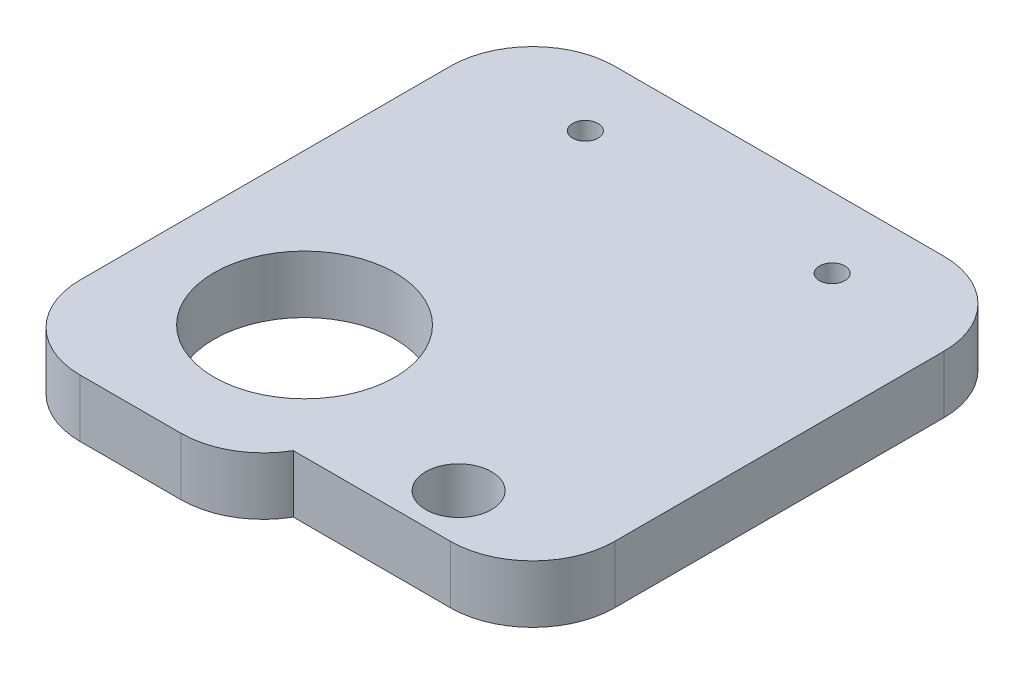
SolidWorks part; units mm, degrees
ref_plane "前视基准面" through (0, 0, 0) normal (0, 0, 1) x (1, 0, 0)
ref_plane "上视基准面" through (0, 0, 0) normal (0, 1, 0) x (1, 0, 0)
ref_plane "右视基准面" through (0, 0, 0) normal (1, 0, 0) x (0, 0, -1)
sketch "草图1" plane through (0, 0, 0) normal (0, 1, 0) x (1, 0, 0)
  line L1 (-25.5, 6.5625) -> (34.5, 6.5625)
  line L2 (-25.5, 6.5625) -> (-25.5, -53.4375)
  line L3 (-25.5, -53.4375) -> (34.5, -53.4375)
  line L4 (34.5, 6.5625) -> (34.5, -53.4375)
  line L5 (-25.5, 6.5625) -> (34.5, -53.4375) construction
  line L6 (-25.5, -53.4375) -> (34.5, 6.5625) construction
  point P4 (4.5, -23.4375)
  dimension "D1" = 60
  dimension "D2" = 60
extrude "凸台-拉伸1" add sketch "草图1" along normal blind 7
sketch "草图2" plane through (0, 0, 0) normal (0, -1, 0) x (1, 0, 0)
  circle A0 centre (19.6799, 47.6056) radius 4
  circle A1 centre (-7.1286, 39.5245) radius 11
  dimension "D1" = 22
  dimension "D2" = 8
extrude "切除-拉伸1" cut sketch "草图2" against normal through all
sketch "草图3" plane through (0, 0, 0) normal (0, -1, 0) x (1, 0, 0)
  line L3 (-25.5, -6.5625) -> (-25.5, 53.4375) construction
  line L4 (34.5, 53.4375) -> (34.5, -6.5625) construction
  circle A0 centre (-10.5, 2.0245) radius 1.55
  circle A1 centre (19.5, 2.0245) radius 1.55
  dimension "D1" = 3.1
  dimension "D2" = 3.1
  dimension "D3" = 15
  dimension "D4" = 15
extrude "切除-拉伸2" cut sketch "草图3" against normal through all
fillet "圆角2" radius 10 3 edges at (34.5, 3.5, 53.4375) (34.5, 3.5, -6.5625) (-25.5, 3.5, -6.5625)
sketch "草图4" plane through (0, 0, 53.4375) normal (0, 0, 1) x (1, 0, 0)
  line L0 (5.4184, 0) -> (5.4184, 7)
  line L1 (-25.5, 0) -> (24.5, 0) construction
  line L2 (-25.5, 7) -> (24.5, 7) construction
  line L3 (5.4184, 7) -> (-25.5, 7)
  line L4 (-25.5, 7) -> (-25.5, 0)
  line L5 (-25.5, 0) -> (5.4184, 0)
extrude "凸台-拉伸2" add sketch "草图4" along normal blind 5
fillet "圆角3" radius 10 2 edges at (5.4184, 3.5, 58.4375) (-25.5, 3.5, 58.4375)
